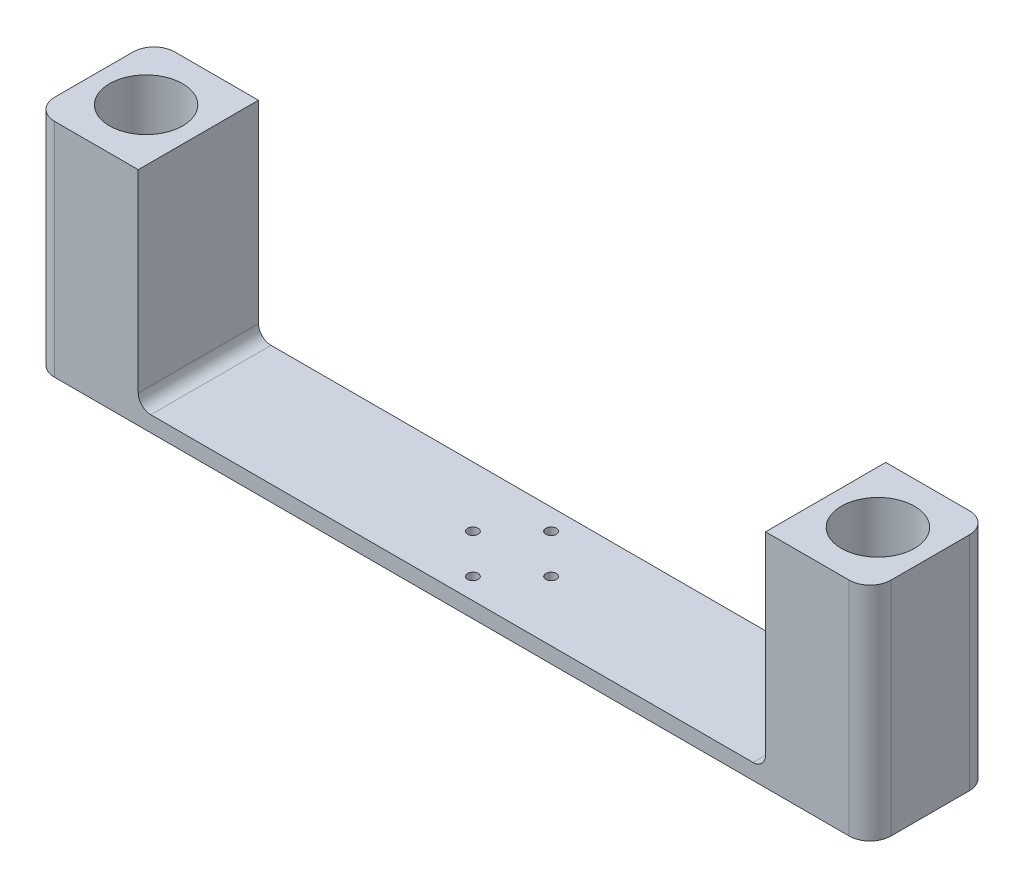
SolidWorks part; units mm, degrees
ref_plane "Front Plane" through (0, 0, 0) normal (0, 0, 1) x (1, 0, 0)
ref_plane "Top Plane" through (0, 0, 0) normal (0, 1, 0) x (1, 0, 0)
ref_plane "Right Plane" through (0, 0, 0) normal (1, 0, 0) x (0, 0, -1)
sketch "Sketch1" plane through (0, 0, 0) normal (0, 1, 0) x (1, 0, 0)
  line L0 (0, 0) -> (0, 4.9523) construction
  line L1 (0, 4.9523) -> (0, 0) construction
  line L2 (0, 0) -> (2.8355, 0) construction
  circle A0 centre (0, 0) radius 13.97
  circle A2 centre (0, 9.5) radius 1.275
  circle A3 centre (9.5, 0) radius 1.275
  circle A4 centre (0, -9.5) radius 1.275
  circle A5 centre (-9.5, 0) radius 1.275
  dimension "D2" = 27.94
  dimension "D3" = 2.55
extrude "Boss-Extrude1" add sketch "Sketch1" along normal blind 3.048
sketch "Sketch2" plane through (0, 3.048, 0) normal (0, 1, 0) x (1, 0, 0)
  line L1 (-96.52, -14.605) -> (96.52, -14.605)
  line L2 (-101.6, -9.525) -> (-101.6, 9.525)
  line L3 (-96.52, 14.605) -> (96.52, 14.605)
  line L4 (101.6, -9.525) -> (101.6, 9.525)
  line L5 (-101.6, -14.605) -> (101.6, 14.605) construction
  line L6 (-101.6, 14.605) -> (101.6, -14.605) construction
  circle A0 centre (-88.9, 0) radius 8.89
  circle A1 centre (88.9, 0) radius 8.89
  arc A3 (96.52, 14.605) -> (101.6, 9.525) centre (96.52, 9.525) cw
  arc A4 (96.52, -14.605) -> (101.6, -9.525) centre (96.52, -9.525) ccw
  arc A5 (-96.52, -14.605) -> (-101.6, -9.525) centre (-96.52, -9.525) cw
  arc A6 (-101.6, 9.525) -> (-96.52, 14.605) centre (-96.52, 9.525) cw
  circle A7 centre (9.5, 0) radius 1.275 construction
  circle A8 centre (0, 9.5) radius 1.275 construction
  circle A9 centre (-9.5, 0) radius 1.275 construction
  circle A10 centre (0, -9.5) radius 1.275 construction
  circle A11 centre (9.5, 0) radius 1.275
  circle A12 centre (0, 9.5) radius 1.275
  circle A13 centre (-9.5, 0) radius 1.275
  circle A14 centre (0, -9.5) radius 1.275
  point P0 (0, 0)
  dimension "D2" = 17.78
  dimension "D3" = 17.78
  dimension "D8" = 5.08
  dimension "D1" = 29.21
  dimension "D4" = 88.9
  dimension "D6" = 12.7
  dimension "D7" = 12.7
extrude "Boss-Extrude2" add sketch "Sketch2" along normal blind 50.8 and the other way through all
sketch "Sketch5" plane through (0, 0, -14.605) normal (0, 0, -1) x (-1, 0, 0)
  line L0 (-101.6, 0) -> (-101.6, 53.848)
  line L1 (-101.6, 53.848) -> (-76.2, 53.848)
  line L2 (-96.52, 53.848) -> (96.52, 53.848) construction
  line L3 (-76.2, 53.848) -> (-76.2, 3.81)
  line L4 (-76.2, 3.81) -> (76.2, 3.81)
  line L5 (0, 3.81) -> (0, 0)
  line L6 (101.6, 0) -> (-101.6, 0)
  line L7 (76.2, 53.848) -> (76.2, 3.81)
  line L8 (101.6, 53.848) -> (76.2, 53.848)
  line L9 (101.6, 0) -> (101.6, 53.848)
  line M8 (96.52, 53.848) -> (-96.52, 53.848)
  dimension "D1" = 25.4
  dimension "D2" = 3.81
extrude "Cut-Extrude2" cut sketch "Sketch5" against normal through all contours L7 L3 L4 M8 region at (0, 28.829, -14.605)
sketch "Sketch6" plane through (0, 0, 0) normal (0, -1, 0) x (1, 0, 0)
  circle A0 centre (-88.9, 0) radius 8.89
  circle A1 centre (-88.9, 0) radius 4.191
  circle A2 centre (88.9, 0) radius 8.89
  circle A3 centre (88.9, 0) radius 4.191
  dimension "D1" = 8.382
  dimension "D2" = 8.382
extrude "Boss-Extrude3" add sketch "Sketch6" against normal blind 4.572
fillet "Fillet2" radius 3.048 2 edges at (76.2, 3.81, 0) (-76.2, 3.81, 0)
